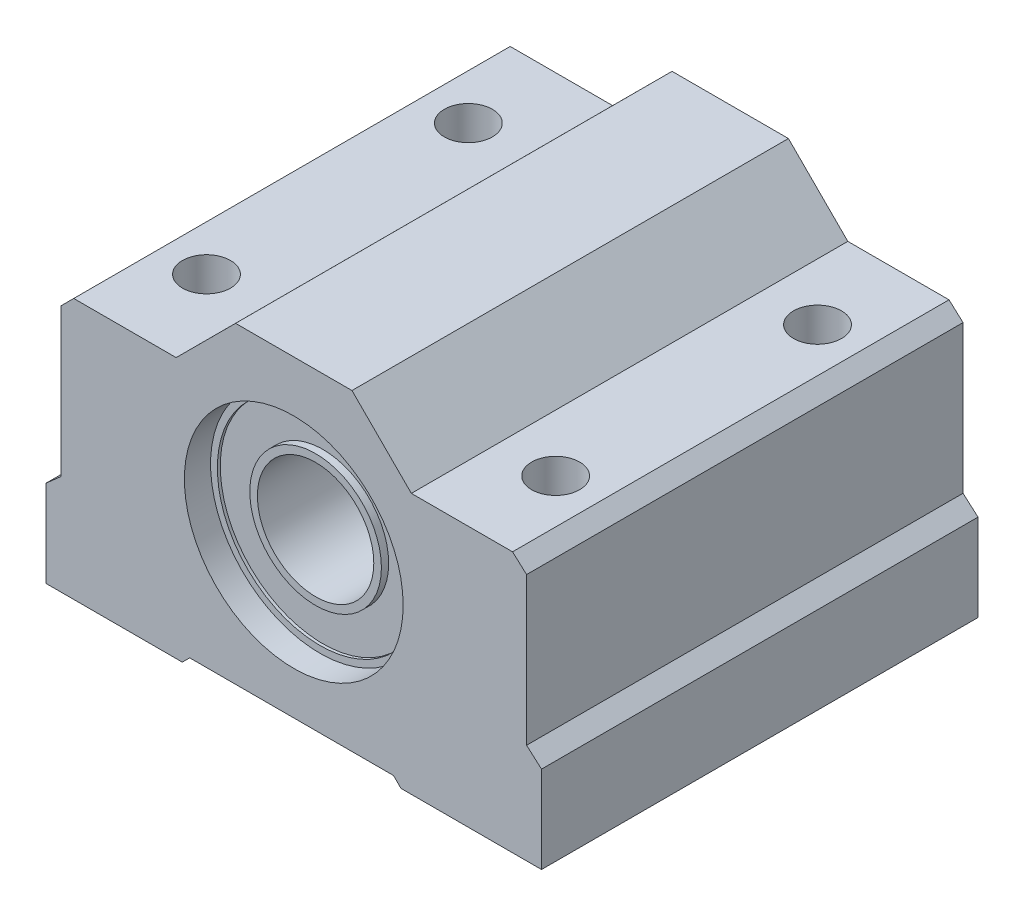
SolidWorks part; units mm, degrees
ref_plane "Plan de face" through (0, 0, 0) normal (0, 0, 1) x (1, 0, 0)
ref_plane "Plan de dessus" through (0, 0, 0) normal (0, 1, 0) x (1, 0, 0)
ref_plane "Plan de droite" through (0, 0, 0) normal (1, 0, 0) x (0, 0, -1)
sketch "Esquisse1" plane through (0, 0, 0) normal (0, 0, 1) x (1, 0, 0)
  line L0 (37.9997, 220.8672) -> (334.6664, 220.8672) construction
  line L1 (-17.03, -10.9738) -> (-7.6627, -10.9738)
  line L2 (-7.6627, -10.9738) -> (-7.1532, -10.4644)
  line L3 (-7.1532, -10.4644) -> (6.8576, -10.4644)
  line L4 (6.8576, -10.4644) -> (7.3671, -10.9738)
  line L5 (7.3671, -10.9738) -> (17.03, -10.9738)
  line L6 (17.03, -10.9738) -> (17.03, -4.9953)
  line L7 (17.03, -4.9953) -> (16.0028, -4.0892)
  line L8 (16.0028, -4.0892) -> (16.0028, 6.0714)
  line L9 (16.0028, 6.0714) -> (15.0375, 6.9443)
  line L10 (15.0375, 6.9443) -> (8.0819, 6.9443)
  line L11 (8.0819, 6.9443) -> (4, 11.0262)
  line L12 (4, 11.0262) -> (-4, 11.0262)
  line L13 (-4, 11.0262) -> (-8.0839, 6.9443)
  line L14 (-8.0839, 6.9443) -> (-15.1244, 6.9443)
  line L15 (-15.1244, 6.9443) -> (-15.9972, 6.0714)
  line L16 (-15.9972, 6.0714) -> (-15.9972, -4.0892)
  line L17 (-15.9972, -4.0892) -> (-17.03, -5.0045)
  line L18 (-17.03, -5.0045) -> (-17.03, -10.9738)
  circle A0 centre (0, 0) radius 4
  circle A1 centre (0, 0) radius 4.5234
  circle A2 centre (0, 0) radius 7.0518
  circle A3 centre (0, 0) radius 7.519
  dimension "D1" = 8
  dimension "D2" = 22
  dimension "D3" = 34.06
  dimension "D4" = 17.03
  dimension "D5" = 32
  dimension "D6" = 8
  dimension "D7" = 4
extrude "Boss.-Extru.1" add sketch "Esquisse1" against normal blind 30 contours L17 L18 L1 L2 L3 L4 L5 L6 L7 L8 L9 L10 L11 L12 L13 L14 L15 L16 A3 region at (-16.6245, -7.9891, 0)
extrude "Boss.-Extru.2" add sketch "Esquisse1<3>" against normal blind 28 separate body contours A2 A1 region at (-6.8523, 0, 0)
sketch "Esquisse1<3>" plane through (0, 0, 0) normal (0, 0, 1) x (1, 0, 0) same geometry as "Esquisse1"
extrude "Boss.-Extru.3" add sketch "Esquisse1<4>" against normal blind 30 contours A3 A2 region at (-7.3063, 0, 0)
sketch "Esquisse1<4>" plane through (0, 0, 0) normal (0, 0, 1) x (1, 0, 0) same geometry as "Esquisse1"
extrude "Boss.-Extru.4" add sketch "Esquisse1<5>" against normal blind 28.5 contours A1 A0 region at (-4.3955, 0, 0)
sketch "Esquisse1<5>" plane through (0, 0, 0) normal (0, 0, 1) x (1, 0, 0) same geometry as "Esquisse1"
extrude "Enlèv. mat.-Extru.1" cut sketch "Esquisse1<6>" against normal blind 1.5 contours A1 A0 region at (-4.3955, 0, 0)
sketch "Esquisse1<6>" plane through (0, 0, 0) normal (0, 0, 1) x (1, 0, 0) same geometry as "Esquisse1"
extrude "Enlèv. mat.-Extru.2" cut sketch "Esquisse1<7>" against normal blind 2 contours A2 A1 region at (-6.8523, 0, 0)
sketch "Esquisse1<7>" plane through (0, 0, 0) normal (0, 0, 1) x (1, 0, 0) same geometry as "Esquisse1"
extrude "Enlèv. mat.-Extru.3" cut sketch "Esquisse1<8>" against normal blind 1.8 contours A3 A2 region at (-7.3063, 0, 0)
sketch "Esquisse1<8>" plane through (0, 0, 0) normal (0, 0, 1) x (1, 0, 0) same geometry as "Esquisse1"
extrude "Enlèv. mat.-Extru.4" cut sketch "Esquisse1<9>" along normal blind 1.8 from surface contours A3 A2 region at (-7.3063, 0, 0) starting at face at (-0.0372, -1.1683, -30)
sketch "Esquisse1<9>" plane through (0, 0, 0) normal (0, 0, 1) x (1, 0, 0) same geometry as "Esquisse1"
sketch "Esquisse2" plane through (0, -10.9738, 0) normal (0, -1, 0) x (1, 0, 0)
  line L0 (74.1667, 293.5) -> (370.8333, 293.5) construction
  line L1 (7.3671, 0) -> (17.03, 0) construction
  line L2 (-17.03, -30) -> (-17.03, 0) construction
  circle A0 centre (-12, -6) radius 1.65
  circle A1 centre (12, -6) radius 1.65
  circle A2 centre (12, -24) radius 1.65
  circle A3 centre (-12, -24) radius 1.65
  dimension "D1" = 3.3
  dimension "D2" = 3.3
  dimension "D3" = 3.3
  dimension "D4" = 3.3
  dimension "D10" = 18
  dimension "D5" = 0
  dimension "D6" = 0
  dimension "D7" = 0
  dimension "D8" = 0
  dimension "D9" = 24
  dimension "D11" = 6
  dimension "D12" = 5.03
extrude "Enlèv. mat.-Extru.5" cut sketch "Esquisse2" against normal blind 21.8
